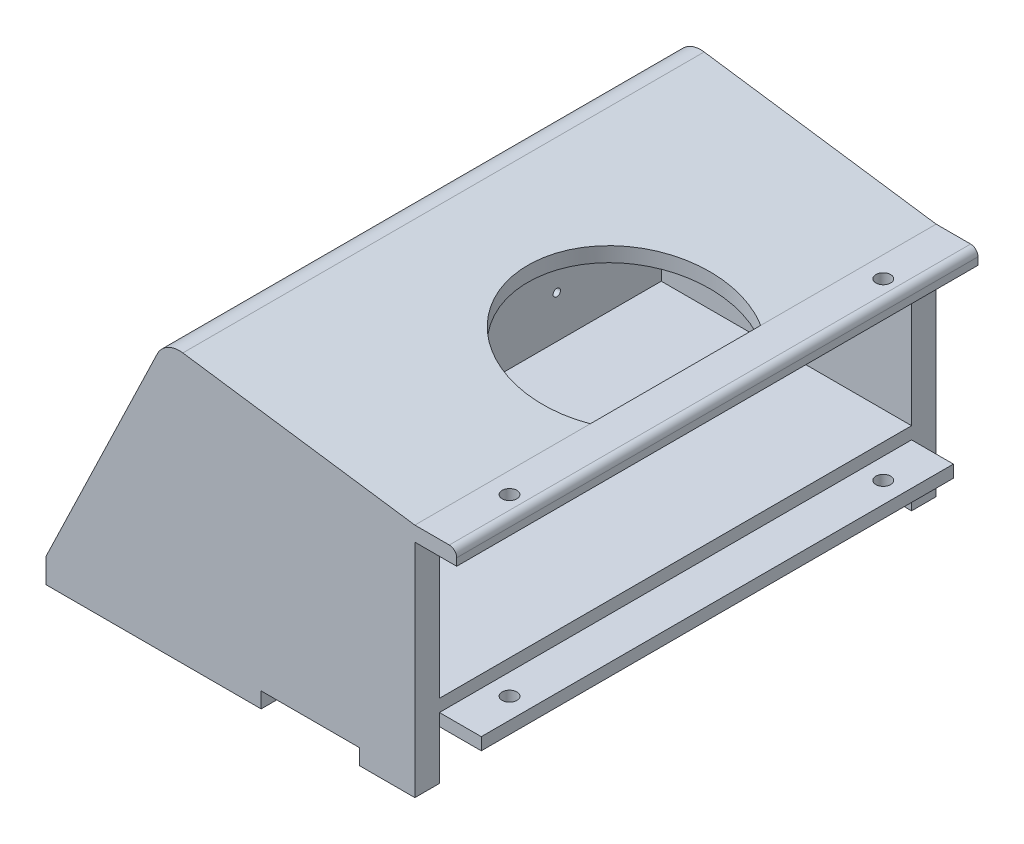
SolidWorks part; units mm, degrees
ref_plane "Front Plane" through (0, 0, 0) normal (0, 0, 1) x (1, 0, 0)
ref_plane "Top Plane" through (0, 0, 0) normal (0, 1, 0) x (1, 0, 0)
ref_plane "Right Plane" through (0, 0, 0) normal (1, 0, 0) x (0, 0, -1)
sketch "Sketch1" plane through (0, 0, 0) normal (0, 0, 1) x (1, 0, 0)
  line L2 (0, 0) -> (0, -6)
  line L7 (-167.02, -86) -> (-167.02, -96)
  line L8 (-167.02, -96) -> (-147.02, -96)
  line L12 (-130.8626, -76) -> (0, -76)
  line L16 (-17.02, -66) -> (-118.8, -66)
  line L20 (-17.02, -66) -> (-17.02, -71)
  line L21 (-17.02, -71) -> (0, -71)
  line L22 (0, -71) -> (0, -76)
  line L26 (0, -66) -> (-93, -66) construction
  line L27 (0, -66) -> (0, -13.5) construction
  line L28 (0, -13.5) -> (-93, -13.5) construction
  line L29 (-93, -66) -> (-93, -13.5) construction
  line L31 (-118.8, -1) -> (-100, -1) construction
  line L32 (-118.8, -1) -> (-118.8, -66) construction
  line L33 (-118.8, -66) -> (-100, -66) construction
  line L34 (-100, -1) -> (-100, -66) construction
  line L39 (-17.02, -6) -> (0, -6)
  line L46 (0, 0) -> (-17.02, 0)
  line L48 (-147.02, -96) -> (-130.8626, -76)
  line L52 (-118.8, -66) -> (-118.8, 8.5183)
  line L53 (-118.8, 8.5183) -> (-17.02, -6)
  line L54 (-17.02, 0) -> (-118.6117, 14.4915)
  line L55 (-118.6117, 14.4915) -> (-167.02, -86)
  dimension "D2" = 20
  dimension "D3" = 7
  dimension "D4" = 10
  dimension "D5" = 5
  dimension "D6" = 6
  dimension "D7" = 20
  dimension "D8" = 5
  dimension "D9" = 65
  dimension "D10" = 52.5
  dimension "D11" = 150
  dimension "D12" = 93
  dimension "D13" = 18.8
  dimension "D14" = 65
  dimension "D18" = 17.02
extrude "Boss-Extrude1" add sketch "Sketch1" along normal blind 212
sketch "Sketch2" plane through (0, -76, 0) normal (0, -1, 0) x (1, 0, 0)
  line L1 (0, 212) -> (-17.02, 212)
  line L2 (0, 212) -> (0, 202)
  line L3 (0, 202) -> (-17.02, 202)
  line L4 (-17.02, 212) -> (-17.02, 202)
  line L5 (0, 0) -> (-17.02, 0)
  line L6 (0, 0) -> (0, 10)
  line L7 (0, 10) -> (-17.02, 10)
  line L8 (-17.02, 0) -> (-17.02, 10)
  dimension "D1" = 10
  dimension "D2" = 17.02
extrude "Cut-Extrude1" cut sketch "Sketch2" against normal up to next
sketch "Sketch3" plane through (-118.8, 0, 0) normal (1, 0, 0) x (0, 0, -1)
  line L0 (-212, -66) -> (-212, 8.5183) construction
  line L1 (-163.5, 3.7683) -> (-48.5, 3.7683) construction
  line L2 (-163.5, 3.7683) -> (-163.5, -61.2317) construction
  line L3 (-163.5, -61.2317) -> (-48.5, -61.2317) construction
  line L4 (-48.5, 3.7683) -> (-48.5, -61.2317) construction
  line L5 (-212, 8.5183) -> (0, 8.5183) construction
  line L8 (-106, -61.2317) -> (-106, -2.1947) construction
  circle A0 centre (-159.5, -8.7317) radius 1.5
  circle A1 centre (-159.5, -48.7317) radius 1.5
  circle A2 centre (-52.5, -48.7317) radius 1.5
  circle A3 centre (-52.5, -8.7317) radius 1.5
  dimension "D1" = 3
  dimension "D2" = 3
  dimension "D7" = 4
  dimension "D3" = 115
  dimension "D4" = 65
  dimension "D5" = 48.5
  dimension "D6" = 4.75
  dimension "D8" = 12.5
  dimension "D9" = 12.5
extrude "Cut-Extrude2" cut sketch "Sketch3" against normal blind 15
sketch "Sketch4" plane through (0, -96, 0) normal (0, 1, 0) x (1, 0, 0)
  line L0 (-147.02, -106) -> (-167.02, -106) construction
  line L4 (-118.6117, 0) -> (-167.02, 0) construction
  line L5 (-167.02, -212) -> (-167.02, 0) construction
  line L6 (-147.02, -212) -> (-147.02, 0) construction
  line L7 (-167.02, -212) -> (-167.02, 0) construction
  circle A1 centre (-157.02, -187) radius 3
  circle A2 centre (-157.02, -25) radius 3
  dimension "D1" = 6
  dimension "D2" = 25
  dimension "D3" = 10
extrude "Cut-Extrude3" cut sketch "Sketch4" against normal through all and the other way through all
sketch "Sketch5" plane through (0, -66, 0) normal (0, 1, 0) x (1, 0, 0)
  line L1 (-113.8, -176.8118) -> (-83.8, -176.8118)
  line L2 (-113.8, -176.8118) -> (-113.8, -191.8118)
  line L3 (-113.8, -191.8118) -> (-83.8, -191.8118)
  line L4 (-83.8, -176.8118) -> (-83.8, -191.8118)
  line L5 (-118.8, -212) -> (-118.8, 0) construction
  dimension "D1" = 15
  dimension "D2" = 5
  dimension "D3" = 30
extrude "Cut-Extrude4" cut sketch "Sketch5" against normal blind 15
sketch "Sketch6" plane through (0, 0, 0) normal (0, 1, 0) x (1, 0, 0)
  line L0 (0, 0) -> (-17.02, 0) construction
  line L2 (-17.02, -106) -> (0, -106) construction
  line L4 (-17.02, -212) -> (-17.02, 0) construction
  line L5 (0, -212) -> (0, 0) construction
  circle A0 centre (-8.52, -30) radius 3
  circle A2 centre (-8.52, -182) radius 3
  dimension "D1" = 6
  dimension "D2" = 30
  dimension "D3" = 8.5
extrude "Cut-Extrude5" cut sketch "Sketch6" against normal through all both and the other way through all
sketch "Sketch7" plane through (0, 0, 212) normal (0, 0, 1) x (1, 0, 0)
  line L2 (-17.02, 0) -> (-118.6117, 14.4915) construction
  line L6 (-167.02, -86) -> (-167.02, -96) construction
  line L7 (-118.6117, 14.4915) -> (-167.02, -86) construction
  line L21 (-17.02, 0) -> (-118.6117, 14.4915)
  line L22 (-167.02, -86) -> (-167.02, -96)
  line L23 (-118.6117, 14.4915) -> (-167.02, -86)
  line L24 (-17.02, 0) -> (-17.02, -96)
  line L25 (-17.02, -96) -> (-167.02, -96)
extrude "Boss-Extrude2" add sketch "Sketch7" against normal blind 10
sketch "Sketch8" plane through (0, 0, 0) normal (0, 0, -1) x (-1, 0, 0)
  line L14 (167.02, -86) -> (167.02, -96) construction
  line L17 (118.6117, 14.4915) -> (167.02, -86) construction
  line L18 (17.02, 0) -> (118.6117, 14.4915) construction
  line L19 (167.02, -86) -> (167.02, -96)
  line L20 (118.6117, 14.4915) -> (167.02, -86)
  line L21 (17.02, 0) -> (118.6117, 14.4915)
  line L22 (17.02, 0) -> (17.02, -96)
  line L23 (17.02, -96) -> (167.02, -96)
extrude "Boss-Extrude3" add sketch "Sketch8" against normal blind 10
sketch "Sketch9" plane through (0, 0, 212) normal (0, 0, 1) x (1, 0, 0)
  line L0 (-167.02, -96) -> (-17.02, -96) construction
  line L1 (-79.52, -96) -> (-39.52, -96)
  line L2 (-79.52, -96) -> (-79.52, -89.65)
  line L3 (-79.52, -89.65) -> (-39.52, -89.65)
  line L4 (-39.52, -96) -> (-39.52, -89.65)
  line L5 (-167.02, -86) -> (-167.02, -96) construction
  dimension "D1" = 87.5
  dimension "D2" = 40
  dimension "D3" = 6.35
extrude "Cut-Extrude6" cut sketch "Sketch9" against normal through all both
sketch "Sketch10" plane through (0, 0, 0) normal (0, 1, 0) x (1, 0, 0)
  line L6 (-17.02, 0) -> (-118.6117, 0) construction
  line L7 (-17.02, -212) -> (-17.02, 0) construction
  line L8 (-17.02, -140.641) -> (-17.02, -71.359)
  arc A2 (-17.02, -71.359) -> (-17.02, -140.641) centre (-37.02, -106) ccw
  dimension "D1" = 106
  dimension "D2" = 20
  dimension "D3" = 80
extrude "Cut-Extrude9" cut sketch "Sketch10" against normal blind 27 and the other way blind 25
ref_plane "Plane1" through (0, -86, 0) normal (0, -1, 0) x (-1, 0, 0)
sketch "Sketch11" plane through (0, -86, 0) normal (0, -1, 0) x (-1, 0, 0)
  line L0 (147.02, -106) -> (167.02, -106) construction
  line L1 (147.02, -202) -> (147.02, -10) construction
  line L2 (167.02, -212) -> (167.02, 0) construction
  circle A0 centre (157.02, -25) radius 7.5
  circle A1 centre (157.02, -187) radius 7.5
  dimension "D1" = 15
extrude "Cut-Extrude10" cut sketch "Sketch11" against normal through all
ref_plane "Plane2" through (-123.8, 0, 0) normal (1, 0, 0) x (0, 0, -1)
sketch "Sketch12" plane through (-123.8, 0, 0) normal (1, 0, 0) x (0, 0, -1)
  circle A0 centre (-159.5, -8.7317) radius 4
  circle A1 centre (-52.5, -8.7317) radius 4
  dimension "D1" = 8
  dimension "D2" = 8
extrude "Cut-Extrude11" cut sketch "Sketch12" against normal through all
fillet "Fillet2" radius 10 1 edges at (-118.6117, 14.4915, 106)
fillet "Fillet3" radius 3 1 edges at (0, 0, 106)
